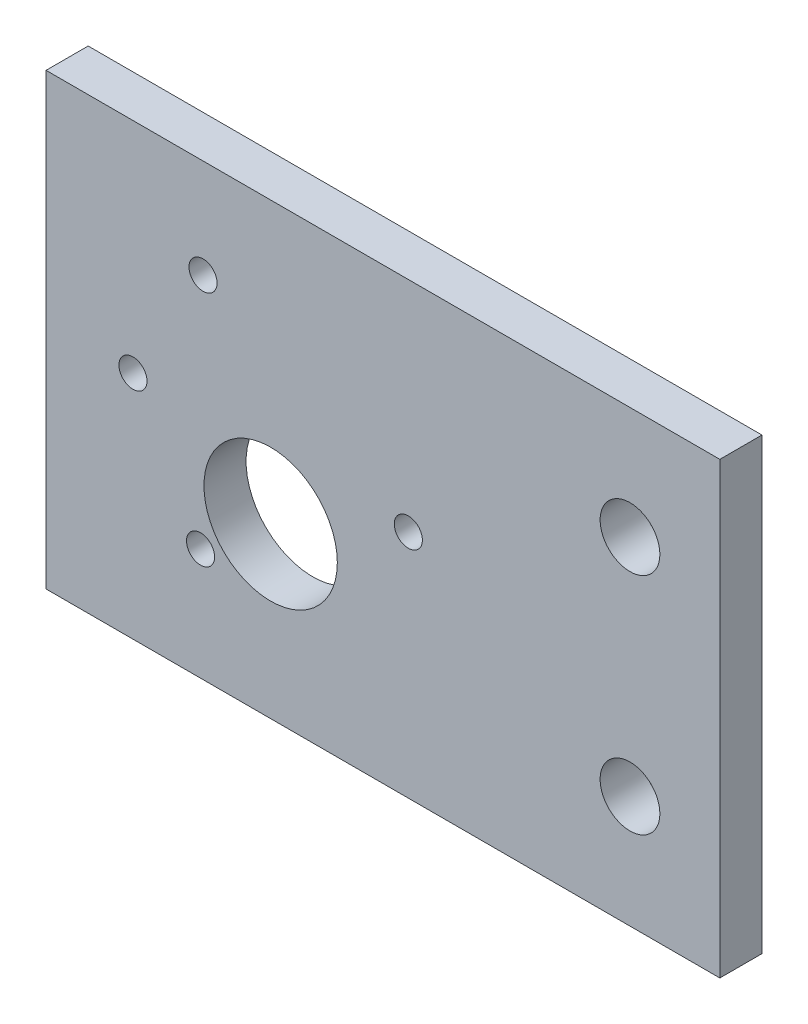
SolidWorks part; units mm, degrees
material "1060 Alloy"
ref_plane "Front" through (0, 0, 0) normal (0, 0, 1) x (1, 0, 0)
ref_plane "Top" through (0, 0, 0) normal (0, 1, 0) x (1, 0, 0)
ref_plane "Right" through (0, 0, 0) normal (1, 0, 0) x (0, 0, -1)
sketch "Sketch1" plane through (0, 0, 0) normal (0, 0, 1) x (1, 0, 0)
  line L1 (-38.1, 25.4) -> (38.1, 25.4)
  line L2 (-38.1, 25.4) -> (-38.1, -25.4)
  line L3 (-38.1, -25.4) -> (38.1, -25.4)
  line L4 (38.1, 25.4) -> (38.1, -25.4)
  line L5 (-38.1, 25.4) -> (38.1, -25.4) construction
  line L6 (-38.1, -25.4) -> (38.1, 25.4) construction
  point P0 (0, 0)
  dimension "D1" = 76.2
  dimension "D2" = 50.8
extrude "Boss-Extrude1" add sketch "Sketch1" along normal blind 4.7625
hole_wizard "19/32 (0.59375) Diameter Hole1" positions "Sketch3" profile "Sketch4" hole size "19/32" standard "ANSI Inch" end condition through all
sketch "Sketch3" plane through (0, 0, 4.7625) normal (0, 0, 1) x (1, 0, 0)
  line L0 (-38.1, 25.4) -> (-38.1, -25.4) construction
  line L1 (38.1, 25.4) -> (-38.1, 25.4) construction
  point P0 (-12.7, -6.35)
  dimension "D1" = 25.4
  dimension "D2" = 31.75
sketch "Sketch4" plane through (-12.7, -6.35, 4.7625) normal (1, 0, 0) x (0, -1, 0)
  line L0 (0, 0) -> (0, 4.7625)
  line L1 (0, 4.7625) -> (7.5406, 4.7625)
  line L2 (7.5406, 4.7625) -> (7.5406, 0)
  line L5 (7.5406, 0) -> (0, 0)
  line L11 (0, -6.35) -> (0, 107.95) construction
  dimension "Thru Hole Dia." = 15.0812
  dimension "Thru Hole Depth" = 4.7625
sketch "Sketch5" plane through (0, 0, 4.7625) normal (0, 0, 1) x (1, 0, 0)
  circle A0 centre (-12.7, 0.6604) radius 15.5702 construction
  circle A1 centre (-12.7, -6.35) radius 7.5406 construction
  circle A2 centre (-12.7, -6.35) radius 7.5406 construction
  dimension "D1" = 31.1404
  dimension "D2" = 7.0104
hole_wizard "1/8 (0.125) Diameter Hole1" positions "Sketch6" profile "Sketch7" hole size "1/8" standard "ANSI Inch" end condition through all
sketch "Sketch6" plane through (0, 0, 4.7625) normal (0, 0, 1) x (1, 0, 0)
  circle A0 centre (-12.7, 0.6604) radius 15.5702 construction
  point P0 (-20.3454, 14.2243)
  point P2 (-28.2702, 0.6604)
  point P4 (-20.6248, -12.7422)
  point P6 (2.8702, 0.6604)
  dimension "D1" = 7.6454
  dimension "D2" = 7.9248
sketch "Sketch7" plane through (-20.3454, 14.2243, 4.7625) normal (1, 0, 0) x (0, -1, 0)
  line L0 (0, 0) -> (0, 4.7625)
  line L1 (0, 4.7625) -> (1.5875, 4.7625)
  line L2 (1.5875, 4.7625) -> (1.5875, 0)
  line L5 (1.5875, 0) -> (0, 0)
  line L11 (0, -6.35) -> (0, 107.95) construction
  dimension "Thru Hole Dia." = 3.175
  dimension "Thru Hole Depth" = 4.7625
hole_wizard "H (0.266) Diameter Hole1" positions "Sketch8" profile "Sketch9" hole size "H" standard "ANSI Inch" end condition through all
sketch "Sketch8" plane through (0, 0, 4.7625) normal (0, 0, 1) x (1, 0, 0)
  line L0 (38.1, -25.4) -> (38.1, 25.4) construction
  line L1 (38.1, 25.4) -> (-38.1, 25.4) construction
  point P0 (27.94, 12.7)
  point P2 (27.94, -12.7)
  dimension "D1" = 10.16
  dimension "D2" = 12.7
  dimension "D3" = 38.1
sketch "Sketch9" plane through (27.94, 12.7, 4.7625) normal (1, 0, 0) x (0, -1, 0)
  line L0 (0, 0) -> (0, 4.7625)
  line L1 (0, 4.7625) -> (3.3782, 4.7625)
  line L2 (3.3782, 4.7625) -> (3.3782, 0)
  line L5 (3.3782, 0) -> (0, 0)
  line L11 (0, -6.35) -> (0, 107.95) construction
  dimension "Thru Hole Dia." = 6.7564
  dimension "Thru Hole Depth" = 4.7625
